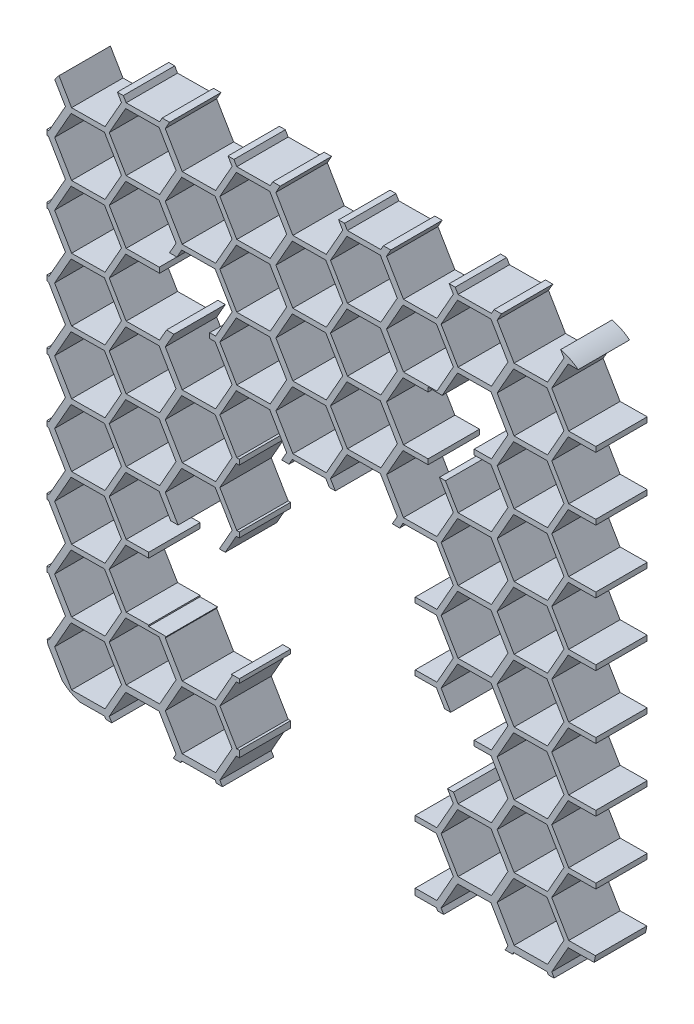
SolidWorks part; units mm, degrees
ref_plane "Front Plane" through (0, 0, 0) normal (0, 0, 1) x (1, 0, 0)
ref_plane "Top Plane" through (0, 0, 0) normal (0, 1, 0) x (1, 0, 0)
ref_plane "Right Plane" through (0, 0, 0) normal (1, 0, 0) x (0, 0, -1)
sketch "Sketch4" plane through (0, 0, 0) normal (0, 0, 1) x (1, 0, 0)
  line L8 (-54.4, 44.4) -> (-54.4, -44.4)
  line L9 (-44.4, -54.4) -> (44.4, -54.4)
  line L10 (54.4, -44.4) -> (54.4, 44.4)
  line L11 (44.4, 54.4) -> (-44.4, 54.4)
  line L12 (-53.4, -44.4) -> (-53.4, 44.4)
  line L13 (-44.4, -53.4) -> (44.4, -53.4)
  line L14 (53.4, -44.4) -> (53.4, 44.4)
  line L15 (-44.4, 53.4) -> (44.4, 53.4)
  arc A8 (-44.4, 54.4) -> (-54.4, 44.4) centre (-44.4, 44.4) ccw
  arc A9 (-54.4, -44.4) -> (-44.4, -54.4) centre (-44.4, -44.4) ccw
  arc A10 (44.4, -54.4) -> (54.4, -44.4) centre (44.4, -44.4) ccw
  arc A11 (54.4, 44.4) -> (44.4, 54.4) centre (44.4, 44.4) ccw
  arc A12 (-53.4, -44.4) -> (-44.4, -53.4) centre (-44.4, -44.4) ccw
  arc A13 (44.4, -53.4) -> (53.4, -44.4) centre (44.4, -44.4) ccw
  arc A14 (53.4, 44.4) -> (44.4, 53.4) centre (44.4, 44.4) ccw
  arc A15 (-44.4, 53.4) -> (-53.4, 44.4) centre (-44.4, 44.4) ccw
sketch "Sketch5" plane through (0, 0, 0) normal (0, 0, 1) x (1, 0, 0)
  line L0 (-28.256, 33.6476) -> (-31.5557, 39.2481)
  line L1 (-38.8735, 27.5176) -> (-42.1732, 33.1181)
  line L2 (-42.1732, 33.1181) -> (-48.6732, 33.0607)
  line L3 (-48.6732, 33.0607) -> (-51.8735, 27.4029)
  line L4 (-51.8735, 27.4029) -> (-48.5738, 21.8024)
  line L5 (-48.5738, 21.8024) -> (-42.0738, 21.8597)
  line L6 (-42.0738, 21.8597) -> (-38.8735, 27.5176)
  line L7 (-31.5557, 39.2481) -> (-38.0557, 39.1907)
  line L8 (-38.0557, 39.1907) -> (-41.256, 33.5329)
  line L9 (-41.256, 33.5329) -> (-37.9563, 27.9324)
  line L10 (-37.9563, 27.9324) -> (-31.4563, 27.9897)
  line L11 (-31.4563, 27.9897) -> (-28.256, 33.6476)
  line L12 (-38.8735, 27.5176) -> (-28.256, 33.6476) construction
  line L13 (-28.256, 45.9076) -> (-31.5557, 51.5081)
  line L14 (-38.8735, 39.7776) -> (-42.1732, 45.3781)
  line L15 (-42.1732, 45.3781) -> (-48.6732, 45.3207)
  line L16 (-48.6732, 45.3207) -> (-51.8735, 39.6629)
  line L17 (-51.8735, 39.6629) -> (-48.5738, 34.0624)
  line L18 (-48.5738, 34.0624) -> (-42.0738, 34.1197)
  line L19 (-42.0738, 34.1197) -> (-38.8735, 39.7776)
  line L20 (-31.5557, 51.5081) -> (-38.0557, 51.4507)
  line L21 (-38.0557, 51.4507) -> (-41.256, 45.7929)
  line L22 (-41.256, 45.7929) -> (-37.9563, 40.1924)
  line L23 (-37.9563, 40.1924) -> (-31.4563, 40.2497)
  line L24 (-31.4563, 40.2497) -> (-28.256, 45.9076)
  line L25 (-38.8735, 39.7776) -> (-28.256, 45.9076) construction
  line L26 (-6.736, 33.6476) -> (-10.0357, 39.2481)
  line L27 (-17.3535, 27.5176) -> (-20.6532, 33.1181)
  line L28 (-20.6532, 33.1181) -> (-27.1532, 33.0607)
  line L29 (-27.1532, 33.0607) -> (-30.3535, 27.4029)
  line L30 (-30.3535, 27.4029) -> (-27.0538, 21.8024)
  line L31 (-27.0538, 21.8024) -> (-20.5538, 21.8597)
  line L32 (-20.5538, 21.8597) -> (-17.3535, 27.5176)
  line L33 (-10.0357, 39.2481) -> (-16.5357, 39.1907)
  line L34 (-16.5357, 39.1907) -> (-19.736, 33.5329)
  line L35 (-19.736, 33.5329) -> (-16.4363, 27.9324)
  line L36 (-16.4363, 27.9324) -> (-9.9363, 27.9897)
  line L37 (-9.9363, 27.9897) -> (-6.736, 33.6476)
  line L38 (-6.736, 45.9076) -> (-10.0357, 51.5081)
  line L39 (-17.3535, 39.7776) -> (-20.6532, 45.3781)
  line L40 (-20.6532, 45.3781) -> (-27.1532, 45.3207)
  line L41 (-27.1532, 45.3207) -> (-30.3535, 39.6629)
  line L42 (-30.3535, 39.6629) -> (-27.0538, 34.0624)
  line L43 (-27.0538, 34.0624) -> (-20.5538, 34.1197)
  line L44 (-20.5538, 34.1197) -> (-17.3535, 39.7776)
  line L45 (-10.0357, 51.5081) -> (-16.5357, 51.4507)
  line L46 (-16.5357, 51.4507) -> (-19.736, 45.7929)
  line L47 (-19.736, 45.7929) -> (-16.4363, 40.1924)
  line L48 (-16.4363, 40.1924) -> (-9.9363, 40.2497)
  line L49 (-9.9363, 40.2497) -> (-6.736, 45.9076)
  line L50 (-17.3535, 27.5176) -> (-6.736, 33.6476) construction
  line L51 (-17.3535, 39.7776) -> (-6.736, 45.9076) construction
  line L52 (14.784, 33.6476) -> (11.4843, 39.2481)
  line L53 (4.1665, 27.5176) -> (0.8668, 33.1181)
  line L54 (0.8668, 33.1181) -> (-5.6332, 33.0607)
  line L55 (-5.6332, 33.0607) -> (-8.8335, 27.4029)
  line L56 (-8.8335, 27.4029) -> (-5.5338, 21.8024)
  line L57 (-5.5338, 21.8024) -> (0.9662, 21.8597)
  line L58 (0.9662, 21.8597) -> (4.1665, 27.5176)
  line L59 (11.4843, 39.2481) -> (4.9843, 39.1907)
  line L60 (4.9843, 39.1907) -> (1.784, 33.5329)
  line L61 (1.784, 33.5329) -> (5.0837, 27.9324)
  line L62 (5.0837, 27.9324) -> (11.5837, 27.9897)
  line L63 (11.5837, 27.9897) -> (14.784, 33.6476)
  line L64 (14.784, 45.9076) -> (11.4843, 51.5081)
  line L65 (4.1665, 39.7776) -> (0.8668, 45.3781)
  line L66 (0.8668, 45.3781) -> (-5.6332, 45.3207)
  line L67 (-5.6332, 45.3207) -> (-8.8335, 39.6629)
  line L68 (-8.8335, 39.6629) -> (-5.5338, 34.0624)
  line L69 (-5.5338, 34.0624) -> (0.9662, 34.1197)
  line L70 (0.9662, 34.1197) -> (4.1665, 39.7776)
  line L71 (11.4843, 51.5081) -> (4.9843, 51.4507)
  line L72 (4.9843, 51.4507) -> (1.784, 45.7929)
  line L73 (1.784, 45.7929) -> (5.0837, 40.1924)
  line L74 (5.0837, 40.1924) -> (11.5837, 40.2497)
  line L75 (11.5837, 40.2497) -> (14.784, 45.9076)
  line L76 (4.1665, 27.5176) -> (14.784, 33.6476) construction
  line L77 (4.1665, 39.7776) -> (14.784, 45.9076) construction
  line L78 (36.304, 33.6476) -> (33.0043, 39.2481)
  line L79 (25.6865, 27.5176) -> (22.3868, 33.1181)
  line L80 (22.3868, 33.1181) -> (15.8868, 33.0607)
  line L81 (15.8868, 33.0607) -> (12.6865, 27.4029)
  line L82 (12.6865, 27.4029) -> (15.9862, 21.8024)
  line L83 (15.9862, 21.8024) -> (22.4862, 21.8597)
  line L84 (22.4862, 21.8597) -> (25.6865, 27.5176)
  line L85 (33.0043, 39.2481) -> (26.5043, 39.1907)
  line L86 (26.5043, 39.1907) -> (23.304, 33.5329)
  line L87 (23.304, 33.5329) -> (26.6037, 27.9324)
  line L88 (26.6037, 27.9324) -> (33.1037, 27.9897)
  line L89 (33.1037, 27.9897) -> (36.304, 33.6476)
  line L90 (36.304, 45.9076) -> (33.0043, 51.5081)
  line L91 (25.6865, 39.7776) -> (22.3868, 45.3781)
  line L92 (22.3868, 45.3781) -> (15.8868, 45.3207)
  line L93 (15.8868, 45.3207) -> (12.6865, 39.6629)
  line L94 (12.6865, 39.6629) -> (15.9862, 34.0624)
  line L95 (15.9862, 34.0624) -> (22.4862, 34.1197)
  line L96 (22.4862, 34.1197) -> (25.6865, 39.7776)
  line L97 (33.0043, 51.5081) -> (26.5043, 51.4507)
  line L98 (26.5043, 51.4507) -> (23.304, 45.7929)
  line L99 (23.304, 45.7929) -> (26.6037, 40.1924)
  line L100 (26.6037, 40.1924) -> (33.1037, 40.2497)
  line L101 (33.1037, 40.2497) -> (36.304, 45.9076)
  line L102 (25.6865, 27.5176) -> (36.304, 33.6476) construction
  line L103 (25.6865, 39.7776) -> (36.304, 45.9076) construction
  line L104 (57.824, 33.6476) -> (54.5243, 39.2481)
  line L105 (47.2065, 27.5176) -> (43.9068, 33.1181)
  line L106 (43.9068, 33.1181) -> (37.4068, 33.0607)
  line L107 (37.4068, 33.0607) -> (34.2065, 27.4029)
  line L108 (34.2065, 27.4029) -> (37.5062, 21.8024)
  line L109 (37.5062, 21.8024) -> (44.0062, 21.8597)
  line L110 (44.0062, 21.8597) -> (47.2065, 27.5176)
  line L111 (54.5243, 39.2481) -> (48.0243, 39.1907)
  line L112 (48.0243, 39.1907) -> (44.824, 33.5329)
  line L113 (44.824, 33.5329) -> (48.1237, 27.9324)
  line L114 (48.1237, 27.9324) -> (54.6237, 27.9897)
  line L115 (54.6237, 27.9897) -> (57.824, 33.6476)
  line L116 (57.824, 45.9076) -> (54.5243, 51.5081)
  line L117 (47.2065, 39.7776) -> (43.9068, 45.3781)
  line L118 (43.9068, 45.3781) -> (37.4068, 45.3207)
  line L119 (37.4068, 45.3207) -> (34.2065, 39.6629)
  line L120 (34.2065, 39.6629) -> (37.5062, 34.0624)
  line L121 (37.5062, 34.0624) -> (44.0062, 34.1197)
  line L122 (44.0062, 34.1197) -> (47.2065, 39.7776)
  line L123 (54.5243, 51.5081) -> (48.0243, 51.4507)
  line L124 (48.0243, 51.4507) -> (44.824, 45.7929)
  line L125 (44.824, 45.7929) -> (48.1237, 40.1924)
  line L126 (48.1237, 40.1924) -> (54.6237, 40.2497)
  line L127 (54.6237, 40.2497) -> (57.824, 45.9076)
  line L128 (47.2065, 27.5176) -> (57.824, 33.6476) construction
  line L129 (47.2065, 39.7776) -> (57.824, 45.9076) construction
  line L130 (-6.736, 9.1276) -> (-10.0357, 14.7281)
  line L131 (-17.3535, 2.9976) -> (-20.6532, 8.5981)
  line L132 (-20.6532, 8.5981) -> (-27.1532, 8.5407)
  line L133 (-27.1532, 8.5407) -> (-30.3535, 2.8829)
  line L134 (-30.3535, 2.8829) -> (-27.0538, -2.7176)
  line L135 (-27.0538, -2.7176) -> (-20.5538, -2.6603)
  line L136 (-20.5538, -2.6603) -> (-17.3535, 2.9976)
  line L137 (-10.0357, 14.7281) -> (-16.5357, 14.6707)
  line L138 (-16.5357, 14.6707) -> (-19.736, 9.0129)
  line L139 (-19.736, 9.0129) -> (-16.4363, 3.4124)
  line L140 (-16.4363, 3.4124) -> (-9.9363, 3.4697)
  line L141 (-9.9363, 3.4697) -> (-6.736, 9.1276)
  line L142 (-6.736, 21.3876) -> (-10.0357, 26.9881)
  line L143 (-17.3535, 15.2576) -> (-20.6532, 20.8581)
  line L144 (-20.6532, 20.8581) -> (-27.1532, 20.8007)
  line L145 (-27.1532, 20.8007) -> (-30.3535, 15.1429)
  line L146 (-30.3535, 15.1429) -> (-27.0538, 9.5424)
  line L147 (-27.0538, 9.5424) -> (-20.5538, 9.5997)
  line L148 (-20.5538, 9.5997) -> (-17.3535, 15.2576)
  line L149 (-10.0357, 26.9881) -> (-16.5357, 26.9307)
  line L150 (-16.5357, 26.9307) -> (-19.736, 21.2729)
  line L151 (-19.736, 21.2729) -> (-16.4363, 15.6724)
  line L152 (-16.4363, 15.6724) -> (-9.9363, 15.7297)
  line L153 (-9.9363, 15.7297) -> (-6.736, 21.3876)
  line L154 (-17.3535, 2.9976) -> (-6.736, 9.1276) construction
  line L155 (-17.3535, 15.2576) -> (-6.736, 21.3876) construction
  line L156 (14.784, 9.1276) -> (11.4843, 14.7281)
  line L157 (4.1665, 2.9976) -> (0.8668, 8.5981)
  line L158 (0.8668, 8.5981) -> (-5.6332, 8.5407)
  line L159 (-5.6332, 8.5407) -> (-8.8335, 2.8829)
  line L160 (-8.8335, 2.8829) -> (-5.5338, -2.7176)
  line L161 (-5.5338, -2.7176) -> (0.9662, -2.6603)
  line L162 (0.9662, -2.6603) -> (4.1665, 2.9976)
  line L163 (11.4843, 14.7281) -> (4.9843, 14.6707)
  line L164 (4.9843, 14.6707) -> (1.784, 9.0129)
  line L165 (1.784, 9.0129) -> (5.0837, 3.4124)
  line L166 (5.0837, 3.4124) -> (11.5837, 3.4697)
  line L167 (11.5837, 3.4697) -> (14.784, 9.1276)
  line L168 (14.784, 21.3876) -> (11.4843, 26.9881)
  line L169 (4.1665, 15.2576) -> (0.8668, 20.8581)
  line L170 (0.8668, 20.8581) -> (-5.6332, 20.8007)
  line L171 (-5.6332, 20.8007) -> (-8.8335, 15.1429)
  line L172 (-8.8335, 15.1429) -> (-5.5338, 9.5424)
  line L173 (-5.5338, 9.5424) -> (0.9662, 9.5997)
  line L174 (0.9662, 9.5997) -> (4.1665, 15.2576)
  line L175 (11.4843, 26.9881) -> (4.9843, 26.9307)
  line L176 (4.9843, 26.9307) -> (1.784, 21.2729)
  line L177 (1.784, 21.2729) -> (5.0837, 15.6724)
  line L178 (5.0837, 15.6724) -> (11.5837, 15.7297)
  line L179 (11.5837, 15.7297) -> (14.784, 21.3876)
  line L180 (4.1665, 2.9976) -> (14.784, 9.1276) construction
  line L181 (4.1665, 15.2576) -> (14.784, 21.3876) construction
  line L182 (36.304, 9.1276) -> (33.0043, 14.7281)
  line L183 (25.6865, 2.9976) -> (22.3868, 8.5981)
  line L184 (22.3868, 8.5981) -> (15.8868, 8.5407)
  line L185 (15.8868, 8.5407) -> (12.6865, 2.8829)
  line L186 (12.6865, 2.8829) -> (15.9862, -2.7176)
  line L187 (15.9862, -2.7176) -> (22.4862, -2.6603)
  line L188 (22.4862, -2.6603) -> (25.6865, 2.9976)
  line L189 (33.0043, 14.7281) -> (26.5043, 14.6707)
  line L190 (26.5043, 14.6707) -> (23.304, 9.0129)
  line L191 (23.304, 9.0129) -> (26.6037, 3.4124)
  line L192 (26.6037, 3.4124) -> (33.1037, 3.4697)
  line L193 (33.1037, 3.4697) -> (36.304, 9.1276)
  line L194 (36.304, 21.3876) -> (33.0043, 26.9881)
  line L195 (25.6865, 15.2576) -> (22.3868, 20.8581)
  line L196 (22.3868, 20.8581) -> (15.8868, 20.8007)
  line L197 (15.8868, 20.8007) -> (12.6865, 15.1429)
  line L198 (12.6865, 15.1429) -> (15.9862, 9.5424)
  line L199 (15.9862, 9.5424) -> (22.4862, 9.5997)
  line L200 (22.4862, 9.5997) -> (25.6865, 15.2576)
  line L201 (33.0043, 26.9881) -> (26.5043, 26.9307)
  line L202 (26.5043, 26.9307) -> (23.304, 21.2729)
  line L203 (23.304, 21.2729) -> (26.6037, 15.6724)
  line L204 (26.6037, 15.6724) -> (33.1037, 15.7297)
  line L205 (33.1037, 15.7297) -> (36.304, 21.3876)
  line L206 (25.6865, 2.9976) -> (36.304, 9.1276) construction
  line L207 (25.6865, 15.2576) -> (36.304, 21.3876) construction
  line L208 (57.824, 9.1276) -> (54.5243, 14.7281)
  line L209 (47.2065, 2.9976) -> (43.9068, 8.5981)
  line L210 (43.9068, 8.5981) -> (37.4068, 8.5407)
  line L211 (37.4068, 8.5407) -> (34.2065, 2.8829)
  line L212 (34.2065, 2.8829) -> (37.5062, -2.7176)
  line L213 (37.5062, -2.7176) -> (44.0062, -2.6603)
  line L214 (44.0062, -2.6603) -> (47.2065, 2.9976)
  line L215 (54.5243, 14.7281) -> (48.0243, 14.6707)
  line L216 (48.0243, 14.6707) -> (44.824, 9.0129)
  line L217 (44.824, 9.0129) -> (48.1237, 3.4124)
  line L218 (48.1237, 3.4124) -> (54.6237, 3.4697)
  line L219 (54.6237, 3.4697) -> (57.824, 9.1276)
  line L220 (57.824, 21.3876) -> (54.5243, 26.9881)
  line L221 (47.2065, 15.2576) -> (43.9068, 20.8581)
  line L222 (43.9068, 20.8581) -> (37.4068, 20.8007)
  line L223 (37.4068, 20.8007) -> (34.2065, 15.1429)
  line L224 (34.2065, 15.1429) -> (37.5062, 9.5424)
  line L225 (37.5062, 9.5424) -> (44.0062, 9.5997)
  line L226 (44.0062, 9.5997) -> (47.2065, 15.2576)
  line L227 (54.5243, 26.9881) -> (48.0243, 26.9307)
  line L228 (48.0243, 26.9307) -> (44.824, 21.2729)
  line L229 (44.824, 21.2729) -> (48.1237, 15.6724)
  line L230 (48.1237, 15.6724) -> (54.6237, 15.7297)
  line L231 (54.6237, 15.7297) -> (57.824, 21.3876)
  line L232 (47.2065, 2.9976) -> (57.824, 9.1276) construction
  line L233 (47.2065, 15.2576) -> (57.824, 21.3876) construction
  line L234 (-6.736, -15.3924) -> (-10.0357, -9.7919)
  line L235 (-17.3535, -21.5224) -> (-20.6532, -15.9219)
  line L236 (-20.6532, -15.9219) -> (-27.1532, -15.9793)
  line L237 (-27.1532, -15.9793) -> (-30.3535, -21.6371)
  line L238 (-30.3535, -21.6371) -> (-27.0538, -27.2376)
  line L239 (-27.0538, -27.2376) -> (-20.5538, -27.1803)
  line L240 (-20.5538, -27.1803) -> (-17.3535, -21.5224)
  line L241 (-10.0357, -9.7919) -> (-16.5357, -9.8493)
  line L242 (-16.5357, -9.8493) -> (-19.736, -15.5071)
  line L243 (-19.736, -15.5071) -> (-16.4363, -21.1076)
  line L244 (-16.4363, -21.1076) -> (-9.9363, -21.0503)
  line L245 (-9.9363, -21.0503) -> (-6.736, -15.3924)
  line L246 (-6.736, -3.1324) -> (-10.0357, 2.4681)
  line L247 (-17.3535, -9.2624) -> (-20.6532, -3.6619)
  line L248 (-20.6532, -3.6619) -> (-27.1532, -3.7193)
  line L249 (-27.1532, -3.7193) -> (-30.3535, -9.3771)
  line L250 (-30.3535, -9.3771) -> (-27.0538, -14.9776)
  line L251 (-27.0538, -14.9776) -> (-20.5538, -14.9203)
  line L252 (-20.5538, -14.9203) -> (-17.3535, -9.2624)
  line L253 (-10.0357, 2.4681) -> (-16.5357, 2.4107)
  line L254 (-16.5357, 2.4107) -> (-19.736, -3.2471)
  line L255 (-19.736, -3.2471) -> (-16.4363, -8.8476)
  line L256 (-16.4363, -8.8476) -> (-9.9363, -8.7903)
  line L257 (-9.9363, -8.7903) -> (-6.736, -3.1324)
  line L258 (-17.3535, -21.5224) -> (-6.736, -15.3924) construction
  line L259 (-17.3535, -9.2624) -> (-6.736, -3.1324) construction
  line L260 (14.784, -15.3924) -> (11.4843, -9.7919)
  line L261 (4.1665, -21.5224) -> (0.8668, -15.9219)
  line L262 (0.8668, -15.9219) -> (-5.6332, -15.9793)
  line L263 (-5.6332, -15.9793) -> (-8.8335, -21.6371)
  line L264 (-8.8335, -21.6371) -> (-5.5338, -27.2376)
  line L265 (-5.5338, -27.2376) -> (0.9662, -27.1803)
  line L266 (0.9662, -27.1803) -> (4.1665, -21.5224)
  line L267 (11.4843, -9.7919) -> (4.9843, -9.8493)
  line L268 (4.9843, -9.8493) -> (1.784, -15.5071)
  line L269 (1.784, -15.5071) -> (5.0837, -21.1076)
  line L270 (5.0837, -21.1076) -> (11.5837, -21.0503)
  line L271 (11.5837, -21.0503) -> (14.784, -15.3924)
  line L272 (14.784, -3.1324) -> (11.4843, 2.4681)
  line L273 (4.1665, -9.2624) -> (0.8668, -3.6619)
  line L274 (0.8668, -3.6619) -> (-5.6332, -3.7193)
  line L275 (-5.6332, -3.7193) -> (-8.8335, -9.3771)
  line L276 (-8.8335, -9.3771) -> (-5.5338, -14.9776)
  line L277 (-5.5338, -14.9776) -> (0.9662, -14.9203)
  line L278 (0.9662, -14.9203) -> (4.1665, -9.2624)
  line L279 (11.4843, 2.4681) -> (4.9843, 2.4107)
  line L280 (4.9843, 2.4107) -> (1.784, -3.2471)
  line L281 (1.784, -3.2471) -> (5.0837, -8.8476)
  line L282 (5.0837, -8.8476) -> (11.5837, -8.7903)
  line L283 (11.5837, -8.7903) -> (14.784, -3.1324)
  line L284 (4.1665, -21.5224) -> (14.784, -15.3924) construction
  line L285 (4.1665, -9.2624) -> (14.784, -3.1324) construction
  line L286 (36.304, -15.3924) -> (33.0043, -9.7919)
  line L287 (25.6865, -21.5224) -> (22.3868, -15.9219)
  line L288 (22.3868, -15.9219) -> (15.8868, -15.9793)
  line L289 (15.8868, -15.9793) -> (12.6865, -21.6371)
  line L290 (12.6865, -21.6371) -> (15.9862, -27.2376)
  line L291 (15.9862, -27.2376) -> (22.4862, -27.1803)
  line L292 (22.4862, -27.1803) -> (25.6865, -21.5224)
  line L293 (33.0043, -9.7919) -> (26.5043, -9.8493)
  line L294 (26.5043, -9.8493) -> (23.304, -15.5071)
  line L295 (23.304, -15.5071) -> (26.6037, -21.1076)
  line L296 (26.6037, -21.1076) -> (33.1037, -21.0503)
  line L297 (33.1037, -21.0503) -> (36.304, -15.3924)
  line L298 (36.304, -3.1324) -> (33.0043, 2.4681)
  line L299 (25.6865, -9.2624) -> (22.3868, -3.6619)
  line L300 (22.3868, -3.6619) -> (15.8868, -3.7193)
  line L301 (15.8868, -3.7193) -> (12.6865, -9.3771)
  line L302 (12.6865, -9.3771) -> (15.9862, -14.9776)
  line L303 (15.9862, -14.9776) -> (22.4862, -14.9203)
  line L304 (22.4862, -14.9203) -> (25.6865, -9.2624)
  line L305 (33.0043, 2.4681) -> (26.5043, 2.4107)
  line L306 (26.5043, 2.4107) -> (23.304, -3.2471)
  line L307 (23.304, -3.2471) -> (26.6037, -8.8476)
  line L308 (26.6037, -8.8476) -> (33.1037, -8.7903)
  line L309 (33.1037, -8.7903) -> (36.304, -3.1324)
  line L310 (25.6865, -21.5224) -> (36.304, -15.3924) construction
  line L311 (25.6865, -9.2624) -> (36.304, -3.1324) construction
  line L312 (57.824, -15.3924) -> (54.5243, -9.7919)
  line L313 (47.2065, -21.5224) -> (43.9068, -15.9219)
  line L314 (43.9068, -15.9219) -> (37.4068, -15.9793)
  line L315 (37.4068, -15.9793) -> (34.2065, -21.6371)
  line L316 (34.2065, -21.6371) -> (37.5062, -27.2376)
  line L317 (37.5062, -27.2376) -> (44.0062, -27.1803)
  line L318 (44.0062, -27.1803) -> (47.2065, -21.5224)
  line L319 (54.5243, -9.7919) -> (48.0243, -9.8493)
  line L320 (48.0243, -9.8493) -> (44.824, -15.5071)
  line L321 (44.824, -15.5071) -> (48.1237, -21.1076)
  line L322 (48.1237, -21.1076) -> (54.6237, -21.0503)
  line L323 (54.6237, -21.0503) -> (57.824, -15.3924)
  line L324 (57.824, -3.1324) -> (54.5243, 2.4681)
  line L325 (47.2065, -9.2624) -> (43.9068, -3.6619)
  line L326 (43.9068, -3.6619) -> (37.4068, -3.7193)
  line L327 (37.4068, -3.7193) -> (34.2065, -9.3771)
  line L328 (34.2065, -9.3771) -> (37.5062, -14.9776)
  line L329 (37.5062, -14.9776) -> (44.0062, -14.9203)
  line L330 (44.0062, -14.9203) -> (47.2065, -9.2624)
  line L331 (54.5243, 2.4681) -> (48.0243, 2.4107)
  line L332 (48.0243, 2.4107) -> (44.824, -3.2471)
  line L333 (44.824, -3.2471) -> (48.1237, -8.8476)
  line L334 (48.1237, -8.8476) -> (54.6237, -8.7903)
  line L335 (54.6237, -8.7903) -> (57.824, -3.1324)
  line L336 (47.2065, -21.5224) -> (57.824, -15.3924) construction
  line L337 (47.2065, -9.2624) -> (57.824, -3.1324) construction
  line L338 (-6.736, -39.9124) -> (-10.0357, -34.3119)
  line L339 (-17.3535, -46.0424) -> (-20.6532, -40.4419)
  line L340 (-20.6532, -40.4419) -> (-27.1532, -40.4993)
  line L341 (-27.1532, -40.4993) -> (-30.3535, -46.1571)
  line L342 (-30.3535, -46.1571) -> (-27.0538, -51.7576)
  line L343 (-27.0538, -51.7576) -> (-20.5538, -51.7003)
  line L344 (-20.5538, -51.7003) -> (-17.3535, -46.0424)
  line L345 (-10.0357, -34.3119) -> (-16.5357, -34.3693)
  line L346 (-16.5357, -34.3693) -> (-19.736, -40.0271)
  line L347 (-19.736, -40.0271) -> (-16.4363, -45.6276)
  line L348 (-16.4363, -45.6276) -> (-9.9363, -45.5703)
  line L349 (-9.9363, -45.5703) -> (-6.736, -39.9124)
  line L350 (-6.736, -27.6524) -> (-10.0357, -22.0519)
  line L351 (-17.3535, -33.7824) -> (-20.6532, -28.1819)
  line L352 (-20.6532, -28.1819) -> (-27.1532, -28.2393)
  line L353 (-27.1532, -28.2393) -> (-30.3535, -33.8971)
  line L354 (-30.3535, -33.8971) -> (-27.0538, -39.4976)
  line L355 (-27.0538, -39.4976) -> (-20.5538, -39.4403)
  line L356 (-20.5538, -39.4403) -> (-17.3535, -33.7824)
  line L357 (-10.0357, -22.0519) -> (-16.5357, -22.1093)
  line L358 (-16.5357, -22.1093) -> (-19.736, -27.7671)
  line L359 (-19.736, -27.7671) -> (-16.4363, -33.3676)
  line L360 (-16.4363, -33.3676) -> (-9.9363, -33.3103)
  line L361 (-9.9363, -33.3103) -> (-6.736, -27.6524)
  line L362 (-17.3535, -46.0424) -> (-6.736, -39.9124) construction
  line L363 (-17.3535, -33.7824) -> (-6.736, -27.6524) construction
  line L364 (14.784, -39.9124) -> (11.4843, -34.3119)
  line L365 (4.1665, -46.0424) -> (0.8668, -40.4419)
  line L366 (0.8668, -40.4419) -> (-5.6332, -40.4993)
  line L367 (-5.6332, -40.4993) -> (-8.8335, -46.1571)
  line L368 (-8.8335, -46.1571) -> (-5.5338, -51.7576)
  line L369 (-5.5338, -51.7576) -> (0.9662, -51.7003)
  line L370 (0.9662, -51.7003) -> (4.1665, -46.0424)
  line L371 (11.4843, -34.3119) -> (4.9843, -34.3693)
  line L372 (4.9843, -34.3693) -> (1.784, -40.0271)
  line L373 (1.784, -40.0271) -> (5.0837, -45.6276)
  line L374 (5.0837, -45.6276) -> (11.5837, -45.5703)
  line L375 (11.5837, -45.5703) -> (14.784, -39.9124)
  line L376 (14.784, -27.6524) -> (11.4843, -22.0519)
  line L377 (4.1665, -33.7824) -> (0.8668, -28.1819)
  line L378 (0.8668, -28.1819) -> (-5.6332, -28.2393)
  line L379 (-5.6332, -28.2393) -> (-8.8335, -33.8971)
  line L380 (-8.8335, -33.8971) -> (-5.5338, -39.4976)
  line L381 (-5.5338, -39.4976) -> (0.9662, -39.4403)
  line L382 (0.9662, -39.4403) -> (4.1665, -33.7824)
  line L383 (11.4843, -22.0519) -> (4.9843, -22.1093)
  line L384 (4.9843, -22.1093) -> (1.784, -27.7671)
  line L385 (1.784, -27.7671) -> (5.0837, -33.3676)
  line L386 (5.0837, -33.3676) -> (11.5837, -33.3103)
  line L387 (11.5837, -33.3103) -> (14.784, -27.6524)
  line L388 (4.1665, -46.0424) -> (14.784, -39.9124) construction
  line L389 (4.1665, -33.7824) -> (14.784, -27.6524) construction
  line L390 (36.304, -39.9124) -> (33.0043, -34.3119)
  line L391 (25.6865, -46.0424) -> (22.3868, -40.4419)
  line L392 (22.3868, -40.4419) -> (15.8868, -40.4993)
  line L393 (15.8868, -40.4993) -> (12.6865, -46.1571)
  line L394 (12.6865, -46.1571) -> (15.9862, -51.7576)
  line L395 (15.9862, -51.7576) -> (22.4862, -51.7003)
  line L396 (22.4862, -51.7003) -> (25.6865, -46.0424)
  line L397 (33.0043, -34.3119) -> (26.5043, -34.3693)
  line L398 (26.5043, -34.3693) -> (23.304, -40.0271)
  line L399 (23.304, -40.0271) -> (26.6037, -45.6276)
  line L400 (26.6037, -45.6276) -> (33.1037, -45.5703)
  line L401 (33.1037, -45.5703) -> (36.304, -39.9124)
  line L402 (36.304, -27.6524) -> (33.0043, -22.0519)
  line L403 (25.6865, -33.7824) -> (22.3868, -28.1819)
  line L404 (22.3868, -28.1819) -> (15.8868, -28.2393)
  line L405 (15.8868, -28.2393) -> (12.6865, -33.8971)
  line L406 (12.6865, -33.8971) -> (15.9862, -39.4976)
  line L407 (15.9862, -39.4976) -> (22.4862, -39.4403)
  line L408 (22.4862, -39.4403) -> (25.6865, -33.7824)
  line L409 (33.0043, -22.0519) -> (26.5043, -22.1093)
  line L410 (26.5043, -22.1093) -> (23.304, -27.7671)
  line L411 (23.304, -27.7671) -> (26.6037, -33.3676)
  line L412 (26.6037, -33.3676) -> (33.1037, -33.3103)
  line L413 (33.1037, -33.3103) -> (36.304, -27.6524)
  line L414 (25.6865, -46.0424) -> (36.304, -39.9124) construction
  line L415 (25.6865, -33.7824) -> (36.304, -27.6524) construction
  line L416 (57.824, -39.9124) -> (54.5243, -34.3119)
  line L417 (47.2065, -46.0424) -> (43.9068, -40.4419)
  line L418 (43.9068, -40.4419) -> (37.4068, -40.4993)
  line L419 (37.4068, -40.4993) -> (34.2065, -46.1571)
  line L420 (34.2065, -46.1571) -> (37.5062, -51.7576)
  line L421 (37.5062, -51.7576) -> (44.0062, -51.7003)
  line L422 (44.0062, -51.7003) -> (47.2065, -46.0424)
  line L423 (54.5243, -34.3119) -> (48.0243, -34.3693)
  line L424 (48.0243, -34.3693) -> (44.824, -40.0271)
  line L425 (44.824, -40.0271) -> (48.1237, -45.6276)
  line L426 (48.1237, -45.6276) -> (54.6237, -45.5703)
  line L427 (54.6237, -45.5703) -> (57.824, -39.9124)
  line L428 (57.824, -27.6524) -> (54.5243, -22.0519)
  line L429 (47.2065, -33.7824) -> (43.9068, -28.1819)
  line L430 (43.9068, -28.1819) -> (37.4068, -28.2393)
  line L431 (37.4068, -28.2393) -> (34.2065, -33.8971)
  line L432 (34.2065, -33.8971) -> (37.5062, -39.4976)
  line L433 (37.5062, -39.4976) -> (44.0062, -39.4403)
  line L434 (44.0062, -39.4403) -> (47.2065, -33.7824)
  line L435 (54.5243, -22.0519) -> (48.0243, -22.1093)
  line L436 (48.0243, -22.1093) -> (44.824, -27.7671)
  line L437 (44.824, -27.7671) -> (48.1237, -33.3676)
  line L438 (48.1237, -33.3676) -> (54.6237, -33.3103)
  line L439 (54.6237, -33.3103) -> (57.824, -27.6524)
  line L440 (47.2065, -46.0424) -> (57.824, -39.9124) construction
  line L441 (47.2065, -33.7824) -> (57.824, -27.6524) construction
  line L442 (-28.256, 9.1276) -> (-31.5557, 14.7281)
  line L443 (-38.8735, 2.9976) -> (-42.1732, 8.5981)
  line L444 (-42.1732, 8.5981) -> (-48.6732, 8.5407)
  line L445 (-48.6732, 8.5407) -> (-51.8735, 2.8829)
  line L446 (-51.8735, 2.8829) -> (-48.5738, -2.7176)
  line L447 (-48.5738, -2.7176) -> (-42.0738, -2.6603)
  line L448 (-42.0738, -2.6603) -> (-38.8735, 2.9976)
  line L449 (-31.5557, 14.7281) -> (-38.0557, 14.6707)
  line L450 (-38.0557, 14.6707) -> (-41.256, 9.0129)
  line L451 (-41.256, 9.0129) -> (-37.9563, 3.4124)
  line L452 (-37.9563, 3.4124) -> (-31.4563, 3.4697)
  line L453 (-31.4563, 3.4697) -> (-28.256, 9.1276)
  line L454 (-28.256, 21.3876) -> (-31.5557, 26.9881)
  line L455 (-38.8735, 15.2576) -> (-42.1732, 20.8581)
  line L456 (-42.1732, 20.8581) -> (-48.6732, 20.8007)
  line L457 (-48.6732, 20.8007) -> (-51.8735, 15.1429)
  line L458 (-51.8735, 15.1429) -> (-48.5738, 9.5424)
  line L459 (-48.5738, 9.5424) -> (-42.0738, 9.5997)
  line L460 (-42.0738, 9.5997) -> (-38.8735, 15.2576)
  line L461 (-31.5557, 26.9881) -> (-38.0557, 26.9307)
  line L462 (-38.0557, 26.9307) -> (-41.256, 21.2729)
  line L463 (-41.256, 21.2729) -> (-37.9563, 15.6724)
  line L464 (-37.9563, 15.6724) -> (-31.4563, 15.7297)
  line L465 (-31.4563, 15.7297) -> (-28.256, 21.3876)
  line L466 (-38.8735, 2.9976) -> (-28.256, 9.1276) construction
  line L467 (-38.8735, 15.2576) -> (-28.256, 21.3876) construction
  line L468 (-28.256, -15.3924) -> (-31.5557, -9.7919)
  line L469 (-38.8735, -21.5224) -> (-42.1732, -15.9219)
  line L470 (-42.1732, -15.9219) -> (-48.6732, -15.9793)
  line L471 (-48.6732, -15.9793) -> (-51.8735, -21.6371)
  line L472 (-51.8735, -21.6371) -> (-48.5738, -27.2376)
  line L473 (-48.5738, -27.2376) -> (-42.0738, -27.1803)
  line L474 (-42.0738, -27.1803) -> (-38.8735, -21.5224)
  line L475 (-31.5557, -9.7919) -> (-38.0557, -9.8493)
  line L476 (-38.0557, -9.8493) -> (-41.256, -15.5071)
  line L477 (-41.256, -15.5071) -> (-37.9563, -21.1076)
  line L478 (-37.9563, -21.1076) -> (-31.4563, -21.0503)
  line L479 (-31.4563, -21.0503) -> (-28.256, -15.3924)
  line L480 (-28.256, -3.1324) -> (-31.5557, 2.4681)
  line L481 (-38.8735, -9.2624) -> (-42.1732, -3.6619)
  line L482 (-42.1732, -3.6619) -> (-48.6732, -3.7193)
  line L483 (-48.6732, -3.7193) -> (-51.8735, -9.3771)
  line L484 (-51.8735, -9.3771) -> (-48.5738, -14.9776)
  line L485 (-48.5738, -14.9776) -> (-42.0738, -14.9203)
  line L486 (-42.0738, -14.9203) -> (-38.8735, -9.2624)
  line L487 (-31.5557, 2.4681) -> (-38.0557, 2.4107)
  line L488 (-38.0557, 2.4107) -> (-41.256, -3.2471)
  line L489 (-41.256, -3.2471) -> (-37.9563, -8.8476)
  line L490 (-37.9563, -8.8476) -> (-31.4563, -8.7903)
  line L491 (-31.4563, -8.7903) -> (-28.256, -3.1324)
  line L492 (-38.8735, -21.5224) -> (-28.256, -15.3924) construction
  line L493 (-38.8735, -9.2624) -> (-28.256, -3.1324) construction
  line L494 (-28.256, -39.9124) -> (-31.5557, -34.3119)
  line L495 (-38.8735, -46.0424) -> (-42.1732, -40.4419)
  line L496 (-42.1732, -40.4419) -> (-48.6732, -40.4993)
  line L497 (-48.6732, -40.4993) -> (-51.8735, -46.1571)
  line L498 (-51.8735, -46.1571) -> (-48.5738, -51.7576)
  line L499 (-48.5738, -51.7576) -> (-42.0738, -51.7003)
  line L500 (-42.0738, -51.7003) -> (-38.8735, -46.0424)
  line L501 (-31.5557, -34.3119) -> (-38.0557, -34.3693)
  line L502 (-38.0557, -34.3693) -> (-41.256, -40.0271)
  line L503 (-41.256, -40.0271) -> (-37.9563, -45.6276)
  line L504 (-37.9563, -45.6276) -> (-31.4563, -45.5703)
  line L505 (-31.4563, -45.5703) -> (-28.256, -39.9124)
  line L506 (-28.256, -27.6524) -> (-31.5557, -22.0519)
  line L507 (-38.8735, -33.7824) -> (-42.1732, -28.1819)
  line L508 (-42.1732, -28.1819) -> (-48.6732, -28.2393)
  line L509 (-48.6732, -28.2393) -> (-51.8735, -33.8971)
  line L510 (-51.8735, -33.8971) -> (-48.5738, -39.4976)
  line L511 (-48.5738, -39.4976) -> (-42.0738, -39.4403)
  line L512 (-42.0738, -39.4403) -> (-38.8735, -33.7824)
  line L513 (-31.5557, -22.0519) -> (-38.0557, -22.1093)
  line L514 (-38.0557, -22.1093) -> (-41.256, -27.7671)
  line L515 (-41.256, -27.7671) -> (-37.9563, -33.3676)
  line L516 (-37.9563, -33.3676) -> (-31.4563, -33.3103)
  line L517 (-31.4563, -33.3103) -> (-28.256, -27.6524)
  line L518 (-38.8735, -46.0424) -> (-28.256, -39.9124) construction
  line L519 (-38.8735, -33.7824) -> (-28.256, -27.6524) construction
  line L520 (-53.4, -44.4) -> (-53.4, 44.4) construction
  line L521 (-44.4, -53.4) -> (44.4, -53.4) construction
  line L522 (53.4, -44.4) -> (53.4, 44.4) construction
  line L523 (-44.4, 53.4) -> (44.4, 53.4) construction
  line L524 (-53.4, -44.4) -> (-53.4, 44.4)
  line L525 (-44.4, -53.4) -> (44.4, -53.4)
  line L526 (53.4, -44.4) -> (53.4, 44.4)
  line L527 (-44.4, 53.4) -> (44.4, 53.4)
  line L528 (-60.3935, 27.5176) -> (-63.6932, 33.1181)
  line L529 (-63.6932, 33.1181) -> (-70.1932, 33.0607)
  line L530 (-70.1932, 33.0607) -> (-73.3935, 27.4029)
  line L531 (-73.3935, 27.4029) -> (-70.0938, 21.8024)
  line L532 (-70.0938, 21.8024) -> (-63.5938, 21.8597)
  line L533 (-63.5938, 21.8597) -> (-60.3935, 27.5176)
  line L534 (-53.0757, 39.2481) -> (-59.5757, 39.1907)
  line L535 (-59.5757, 39.1907) -> (-62.776, 33.5329)
  line L536 (-62.776, 33.5329) -> (-59.4763, 27.9324)
  line L537 (-59.4763, 27.9324) -> (-52.9763, 27.9897)
  line L538 (-60.3935, 39.7776) -> (-63.6932, 45.3781)
  line L539 (-63.6932, 45.3781) -> (-70.1932, 45.3207)
  line L540 (-70.1932, 45.3207) -> (-73.3935, 39.6629)
  line L541 (-73.3935, 39.6629) -> (-70.0938, 34.0624)
  line L542 (-70.0938, 34.0624) -> (-63.5938, 34.1197)
  line L543 (-63.5938, 34.1197) -> (-60.3935, 39.7776)
  line L544 (-53.0757, 51.5081) -> (-59.5757, 51.4507)
  line L545 (-59.5757, 51.4507) -> (-62.776, 45.7929)
  line L546 (-62.776, 45.7929) -> (-59.4763, 40.1924)
  line L547 (-59.4763, 40.1924) -> (-52.9763, 40.2497)
  line L548 (-60.3935, 2.9976) -> (-63.6932, 8.5981)
  line L549 (-63.6932, 8.5981) -> (-70.1932, 8.5407)
  line L550 (-70.1932, 8.5407) -> (-73.3935, 2.8829)
  line L551 (-73.3935, 2.8829) -> (-70.0938, -2.7176)
  line L552 (-70.0938, -2.7176) -> (-63.5938, -2.6603)
  line L553 (-63.5938, -2.6603) -> (-60.3935, 2.9976)
  line L554 (-53.0757, 14.7281) -> (-59.5757, 14.6707)
  line L555 (-59.5757, 14.6707) -> (-62.776, 9.0129)
  line L556 (-62.776, 9.0129) -> (-59.4763, 3.4124)
  line L557 (-59.4763, 3.4124) -> (-52.9763, 3.4697)
  line L558 (-60.3935, 15.2576) -> (-63.6932, 20.8581)
  line L559 (-63.6932, 20.8581) -> (-70.1932, 20.8007)
  line L560 (-70.1932, 20.8007) -> (-73.3935, 15.1429)
  line L561 (-73.3935, 15.1429) -> (-70.0938, 9.5424)
  line L562 (-70.0938, 9.5424) -> (-63.5938, 9.5997)
  line L563 (-63.5938, 9.5997) -> (-60.3935, 15.2576)
  line L564 (-53.0757, 26.9881) -> (-59.5757, 26.9307)
  line L565 (-59.5757, 26.9307) -> (-62.776, 21.2729)
  line L566 (-62.776, 21.2729) -> (-59.4763, 15.6724)
  line L567 (-59.4763, 15.6724) -> (-52.9763, 15.7297)
  line L568 (-60.3935, -21.5224) -> (-63.6932, -15.9219)
  line L569 (-63.6932, -15.9219) -> (-70.1932, -15.9793)
  line L570 (-70.1932, -15.9793) -> (-73.3935, -21.6371)
  line L571 (-73.3935, -21.6371) -> (-70.0938, -27.2376)
  line L572 (-70.0938, -27.2376) -> (-63.5938, -27.1803)
  line L573 (-63.5938, -27.1803) -> (-60.3935, -21.5224)
  line L574 (-53.0757, -9.7919) -> (-59.5757, -9.8493)
  line L575 (-59.5757, -9.8493) -> (-62.776, -15.5071)
  line L576 (-62.776, -15.5071) -> (-59.4763, -21.1076)
  line L577 (-59.4763, -21.1076) -> (-52.9763, -21.0503)
  line L578 (-60.3935, -9.2624) -> (-63.6932, -3.6619)
  line L579 (-63.6932, -3.6619) -> (-70.1932, -3.7193)
  line L580 (-70.1932, -3.7193) -> (-73.3935, -9.3771)
  line L581 (-73.3935, -9.3771) -> (-70.0938, -14.9776)
  line L582 (-70.0938, -14.9776) -> (-63.5938, -14.9203)
  line L583 (-63.5938, -14.9203) -> (-60.3935, -9.2624)
  line L584 (-53.0757, 2.4681) -> (-59.5757, 2.4107)
  line L585 (-59.5757, 2.4107) -> (-62.776, -3.2471)
  line L586 (-62.776, -3.2471) -> (-59.4763, -8.8476)
  line L587 (-59.4763, -8.8476) -> (-52.9763, -8.7903)
  line L588 (-60.3935, -46.0424) -> (-63.6932, -40.4419)
  line L589 (-63.6932, -40.4419) -> (-70.1932, -40.4993)
  line L590 (-70.1932, -40.4993) -> (-73.3935, -46.1571)
  line L591 (-73.3935, -46.1571) -> (-70.0938, -51.7576)
  line L592 (-63.5938, -51.7003) -> (-60.3935, -46.0424)
  line L593 (-53.0757, -34.3119) -> (-59.5757, -34.3693)
  line L594 (-59.5757, -34.3693) -> (-62.776, -40.0271)
  line L595 (-62.776, -40.0271) -> (-59.4763, -45.6276)
  line L596 (-59.4763, -45.6276) -> (-52.9763, -45.5703)
  line L597 (-60.3935, -33.7824) -> (-63.6932, -28.1819)
  line L598 (-63.6932, -28.1819) -> (-70.1932, -28.2393)
  line L599 (-70.1932, -28.2393) -> (-73.3935, -33.8971)
  line L600 (-73.3935, -33.8971) -> (-70.0938, -39.4976)
  line L601 (-70.0938, -39.4976) -> (-63.5938, -39.4403)
  line L602 (-63.5938, -39.4403) -> (-60.3935, -33.7824)
  line L603 (-53.0757, -22.0519) -> (-59.5757, -22.1093)
  line L604 (-59.5757, -22.1093) -> (-62.776, -27.7671)
  line L605 (-62.776, -27.7671) -> (-59.4763, -33.3676)
  line L606 (-59.4763, -33.3676) -> (-52.9763, -33.3103)
  line L607 (-60.3935, 27.5176) -> (-49.776, 33.6476) construction
  line L608 (-60.3935, 39.7776) -> (-49.776, 45.9076) construction
  line L609 (-60.3935, 2.9976) -> (-49.776, 9.1276) construction
  line L610 (-60.3935, 15.2576) -> (-49.776, 21.3876) construction
  line L611 (-60.3935, -21.5224) -> (-49.776, -15.3924) construction
  line L612 (-60.3935, -9.2624) -> (-49.776, -3.1324) construction
  line L613 (-60.3935, -46.0424) -> (-49.776, -39.9124) construction
  line L614 (-60.3935, -33.7824) -> (-49.776, -27.6524) construction
  line L615 (-70.0938, -51.7576) -> (-63.5938, -51.7003)
  line L616 (-52.9763, 3.4697) -> (-49.776, 9.1276)
  line L617 (-49.776, 9.1276) -> (-53.0757, 14.7281)
  line L618 (-52.9763, 15.7297) -> (-49.776, 21.3876)
  line L619 (-49.776, 21.3876) -> (-53.0757, 26.9881)
  line L620 (-52.9763, 27.9897) -> (-49.776, 33.6476)
  line L621 (-49.776, 33.6476) -> (-53.0757, 39.2481)
  line L622 (-52.9763, 40.2497) -> (-49.776, 45.9076)
  line L623 (-49.776, 45.9076) -> (-53.0757, 51.5081)
  line L624 (-49.776, -3.1324) -> (-53.0757, 2.4681)
  line L625 (-52.9763, -8.7903) -> (-49.776, -3.1324)
  line L626 (-49.776, -15.3924) -> (-53.0757, -9.7919)
  line L627 (-52.9763, -21.0503) -> (-49.776, -15.3924)
  line L628 (-49.776, -27.6524) -> (-53.0757, -22.0519)
  line L629 (-52.9763, -33.3103) -> (-49.776, -27.6524)
  line L630 (-49.776, -39.9124) -> (-53.0757, -34.3119)
  line L631 (-52.9763, -45.5703) -> (-49.776, -39.9124)
  line L632 (-6.736, -52.4324) -> (-10.0357, -46.8319)
  line L633 (-17.3535, -58.5624) -> (-20.6532, -52.9619)
  line L634 (-20.6532, -52.9619) -> (-27.1532, -53.0193)
  line L635 (-27.1532, -53.0193) -> (-30.3535, -58.6771)
  line L636 (-30.3535, -58.6771) -> (-27.0538, -64.2776)
  line L637 (-27.0538, -64.2776) -> (-20.5538, -64.2203)
  line L638 (-20.5538, -64.2203) -> (-17.3535, -58.5624)
  line L639 (-16.5357, -46.8893) -> (-19.736, -52.5471)
  line L640 (-19.736, -52.5471) -> (-16.4363, -58.1476)
  line L641 (-16.4363, -58.1476) -> (-9.9363, -58.0903)
  line L642 (-9.9363, -58.0903) -> (-6.736, -52.4324)
  line L643 (14.784, -52.4324) -> (11.4843, -46.8319)
  line L644 (4.1665, -58.5624) -> (0.8668, -52.9619)
  line L645 (0.8668, -52.9619) -> (-5.6332, -53.0193)
  line L646 (-5.6332, -53.0193) -> (-8.8335, -58.6771)
  line L647 (-8.8335, -58.6771) -> (-5.5338, -64.2776)
  line L648 (-5.5338, -64.2776) -> (0.9662, -64.2203)
  line L649 (0.9662, -64.2203) -> (4.1665, -58.5624)
  line L650 (4.9843, -46.8893) -> (1.784, -52.5471)
  line L651 (1.784, -52.5471) -> (5.0837, -58.1476)
  line L652 (5.0837, -58.1476) -> (11.5837, -58.0903)
  line L653 (11.5837, -58.0903) -> (14.784, -52.4324)
  line L654 (36.304, -52.4324) -> (33.0043, -46.8319)
  line L655 (25.6865, -58.5624) -> (22.3868, -52.9619)
  line L656 (22.3868, -52.9619) -> (15.8868, -53.0193)
  line L657 (15.8868, -53.0193) -> (12.6865, -58.6771)
  line L658 (12.6865, -58.6771) -> (15.9862, -64.2776)
  line L659 (15.9862, -64.2776) -> (22.4862, -64.2203)
  line L660 (22.4862, -64.2203) -> (25.6865, -58.5624)
  line L661 (26.5043, -46.8893) -> (23.304, -52.5471)
  line L662 (23.304, -52.5471) -> (26.6037, -58.1476)
  line L663 (26.6037, -58.1476) -> (33.1037, -58.0903)
  line L664 (33.1037, -58.0903) -> (36.304, -52.4324)
  line L665 (57.824, -52.4324) -> (54.5243, -46.8319)
  line L666 (47.2065, -58.5624) -> (43.9068, -52.9619)
  line L667 (43.9068, -52.9619) -> (37.4068, -53.0193)
  line L668 (37.4068, -53.0193) -> (34.2065, -58.6771)
  line L669 (34.2065, -58.6771) -> (37.5062, -64.2776)
  line L670 (37.5062, -64.2776) -> (44.0062, -64.2203)
  line L671 (44.0062, -64.2203) -> (47.2065, -58.5624)
  line L672 (48.0243, -46.8893) -> (44.824, -52.5471)
  line L673 (44.824, -52.5471) -> (48.1237, -58.1476)
  line L674 (48.1237, -58.1476) -> (54.6237, -58.0903)
  line L675 (54.6237, -58.0903) -> (57.824, -52.4324)
  line L676 (-28.256, -52.4324) -> (-31.5557, -46.8319)
  line L677 (-38.8735, -58.5624) -> (-42.1732, -52.9619)
  line L678 (-42.1732, -52.9619) -> (-48.6732, -53.0193)
  line L679 (-48.6732, -53.0193) -> (-51.8735, -58.6771)
  line L680 (-51.8735, -58.6771) -> (-48.5738, -64.2776)
  line L681 (-48.5738, -64.2776) -> (-42.0738, -64.2203)
  line L682 (-42.0738, -64.2203) -> (-38.8735, -58.5624)
  line L683 (-38.0557, -46.8893) -> (-41.256, -52.5471)
  line L684 (-41.256, -52.5471) -> (-37.9563, -58.1476)
  line L685 (-37.9563, -58.1476) -> (-31.4563, -58.0903)
  line L686 (-31.4563, -58.0903) -> (-28.256, -52.4324)
  line L687 (-17.3535, -58.5624) -> (-6.736, -52.4324) construction
  line L688 (4.1665, -58.5624) -> (14.784, -52.4324) construction
  line L689 (25.6865, -58.5624) -> (36.304, -52.4324) construction
  line L690 (47.2065, -58.5624) -> (57.824, -52.4324) construction
  line L691 (-38.8735, -58.5624) -> (-28.256, -52.4324) construction
  line L692 (-60.3935, -58.5624) -> (-49.776, -52.4324) construction
  line L693 (-31.5557, -46.8319) -> (-38.0557, -46.8893)
  line L694 (-10.0357, -46.8319) -> (-16.5357, -46.8893)
  line L695 (11.4843, -46.8319) -> (4.9843, -46.8893)
  line L696 (33.0043, -46.8319) -> (26.5043, -46.8893)
  line L697 (54.5243, -46.8319) -> (48.0243, -46.8893)
  line L698 (-38.8735, 52.0376) -> (-42.1732, 57.6381)
  line L699 (-42.1732, 57.6381) -> (-48.6732, 57.5807)
  line L700 (-48.6732, 57.5807) -> (-51.8735, 51.9229)
  line L701 (-51.8735, 51.9229) -> (-48.5738, 46.3224)
  line L702 (-48.5738, 46.3224) -> (-42.0738, 46.3797)
  line L703 (-42.0738, 46.3797) -> (-38.8735, 52.0376)
  line L704 (-17.3535, 52.0376) -> (-20.6532, 57.6381)
  line L705 (-20.6532, 57.6381) -> (-27.1532, 57.5807)
  line L706 (-27.1532, 57.5807) -> (-30.3535, 51.9229)
  line L707 (-30.3535, 51.9229) -> (-27.0538, 46.3224)
  line L708 (-27.0538, 46.3224) -> (-20.5538, 46.3797)
  line L709 (-20.5538, 46.3797) -> (-17.3535, 52.0376)
  line L710 (4.1665, 52.0376) -> (0.8668, 57.6381)
  line L711 (0.8668, 57.6381) -> (-5.6332, 57.5807)
  line L712 (-5.6332, 57.5807) -> (-8.8335, 51.9229)
  line L713 (-8.8335, 51.9229) -> (-5.5338, 46.3224)
  line L714 (-5.5338, 46.3224) -> (0.9662, 46.3797)
  line L715 (0.9662, 46.3797) -> (4.1665, 52.0376)
  line L716 (25.6865, 52.0376) -> (22.3868, 57.6381)
  line L717 (22.3868, 57.6381) -> (15.8868, 57.5807)
  line L718 (15.8868, 57.5807) -> (12.6865, 51.9229)
  line L719 (12.6865, 51.9229) -> (15.9862, 46.3224)
  line L720 (15.9862, 46.3224) -> (22.4862, 46.3797)
  line L721 (22.4862, 46.3797) -> (25.6865, 52.0376)
  line L722 (47.2065, 52.0376) -> (43.9068, 57.6381)
  line L723 (43.9068, 57.6381) -> (37.4068, 57.5807)
  line L724 (37.4068, 57.5807) -> (34.2065, 51.9229)
  line L725 (34.2065, 51.9229) -> (37.5062, 46.3224)
  line L726 (37.5062, 46.3224) -> (44.0062, 46.3797)
  line L727 (44.0062, 46.3797) -> (47.2065, 52.0376)
  line L728 (-28.256, 58.1676) -> (-31.5557, 63.7681)
  line L729 (-31.5557, 63.7681) -> (-38.0557, 63.7107)
  line L730 (-38.0557, 63.7107) -> (-41.256, 58.0529)
  line L731 (-41.256, 58.0529) -> (-37.9563, 52.4524)
  line L732 (-37.9563, 52.4524) -> (-31.4563, 52.5097)
  line L733 (-31.4563, 52.5097) -> (-28.256, 58.1676)
  line L734 (-6.736, 58.1676) -> (-10.0357, 63.7681)
  line L735 (-10.0357, 63.7681) -> (-16.5357, 63.7107)
  line L736 (-16.5357, 63.7107) -> (-19.736, 58.0529)
  line L737 (-19.736, 58.0529) -> (-16.4363, 52.4524)
  line L738 (-16.4363, 52.4524) -> (-9.9363, 52.5097)
  line L739 (-9.9363, 52.5097) -> (-6.736, 58.1676)
  line L740 (14.784, 58.1676) -> (11.4843, 63.7681)
  line L741 (11.4843, 63.7681) -> (4.9843, 63.7107)
  line L742 (4.9843, 63.7107) -> (1.784, 58.0529)
  line L743 (1.784, 58.0529) -> (5.0837, 52.4524)
  line L744 (5.0837, 52.4524) -> (11.5837, 52.5097)
  line L745 (11.5837, 52.5097) -> (14.784, 58.1676)
  line L746 (36.304, 58.1676) -> (33.0043, 63.7681)
  line L747 (33.0043, 63.7681) -> (26.5043, 63.7107)
  line L748 (26.5043, 63.7107) -> (23.304, 58.0529)
  line L749 (23.304, 58.0529) -> (26.6037, 52.4524)
  line L750 (26.6037, 52.4524) -> (33.1037, 52.5097)
  line L751 (33.1037, 52.5097) -> (36.304, 58.1676)
  line L752 (-53.0757, -46.5719) -> (-59.5757, -46.6293)
  line L753 (-59.5757, -46.6293) -> (-62.776, -52.2871)
  line L754 (-62.776, -52.2871) -> (-59.4763, -57.8876)
  line L755 (-59.4763, -57.8876) -> (-52.9763, -57.8303)
  line L756 (-52.9763, -57.8303) -> (-49.776, -52.1724)
  line L757 (-49.776, -52.1724) -> (-53.0757, -46.5719)
  circle A0 centre (-45.3735, 27.4602) radius 5.6294 construction
  circle A1 centre (-34.756, 33.5902) radius 5.6294 construction
  circle A2 centre (-45.3735, 39.7202) radius 5.6294 construction
  circle A3 centre (-34.756, 45.8502) radius 5.6294 construction
  circle A4 centre (-23.8535, 27.4602) radius 5.6294 construction
  circle A5 centre (-13.236, 33.5902) radius 5.6294 construction
  circle A6 centre (-23.8535, 39.7202) radius 5.6294 construction
  circle A7 centre (-13.236, 45.8502) radius 5.6294 construction
  circle A8 centre (-2.3335, 27.4602) radius 5.6294 construction
  circle A9 centre (8.284, 33.5902) radius 5.6294 construction
  circle A10 centre (-2.3335, 39.7202) radius 5.6294 construction
  circle A11 centre (8.284, 45.8502) radius 5.6294 construction
  circle A12 centre (19.1865, 27.4602) radius 5.6294 construction
  circle A13 centre (29.804, 33.5902) radius 5.6294 construction
  circle A14 centre (19.1865, 39.7202) radius 5.6294 construction
  circle A15 centre (29.804, 45.8502) radius 5.6294 construction
  circle A16 centre (40.7065, 27.4602) radius 5.6294 construction
  circle A17 centre (51.324, 33.5902) radius 5.6294 construction
  circle A18 centre (40.7065, 39.7202) radius 5.6294 construction
  circle A19 centre (51.324, 45.8502) radius 5.6294 construction
  circle A20 centre (-23.8535, 2.9402) radius 5.6294 construction
  circle A21 centre (-13.236, 9.0702) radius 5.6294 construction
  circle A22 centre (-23.8535, 15.2002) radius 5.6294 construction
  circle A23 centre (-13.236, 21.3302) radius 5.6294 construction
  circle A24 centre (-2.3335, 2.9402) radius 5.6294 construction
  circle A25 centre (8.284, 9.0702) radius 5.6294 construction
  circle A26 centre (-2.3335, 15.2002) radius 5.6294 construction
  circle A27 centre (8.284, 21.3302) radius 5.6294 construction
  circle A28 centre (19.1865, 2.9402) radius 5.6294 construction
  circle A29 centre (29.804, 9.0702) radius 5.6294 construction
  circle A30 centre (19.1865, 15.2002) radius 5.6294 construction
  circle A31 centre (29.804, 21.3302) radius 5.6294 construction
  circle A32 centre (40.7065, 2.9402) radius 5.6294 construction
  circle A33 centre (51.324, 9.0702) radius 5.6294 construction
  circle A34 centre (40.7065, 15.2002) radius 5.6294 construction
  circle A35 centre (51.324, 21.3302) radius 5.6294 construction
  circle A36 centre (-23.8535, -21.5798) radius 5.6294 construction
  circle A37 centre (-13.236, -15.4498) radius 5.6294 construction
  circle A38 centre (-23.8535, -9.3198) radius 5.6294 construction
  circle A39 centre (-13.236, -3.1898) radius 5.6294 construction
  circle A40 centre (-2.3335, -21.5798) radius 5.6294 construction
  circle A41 centre (8.284, -15.4498) radius 5.6294 construction
  circle A42 centre (-2.3335, -9.3198) radius 5.6294 construction
  circle A43 centre (8.284, -3.1898) radius 5.6294 construction
  circle A44 centre (19.1865, -21.5798) radius 5.6294 construction
  circle A45 centre (29.804, -15.4498) radius 5.6294 construction
  circle A46 centre (19.1865, -9.3198) radius 5.6294 construction
  circle A47 centre (29.804, -3.1898) radius 5.6294 construction
  circle A48 centre (40.7065, -21.5798) radius 5.6294 construction
  circle A49 centre (51.324, -15.4498) radius 5.6294 construction
  circle A50 centre (40.7065, -9.3198) radius 5.6294 construction
  circle A51 centre (51.324, -3.1898) radius 5.6294 construction
  circle A52 centre (-23.8535, -46.0998) radius 5.6294 construction
  circle A53 centre (-13.236, -39.9698) radius 5.6294 construction
  circle A54 centre (-23.8535, -33.8398) radius 5.6294 construction
  circle A55 centre (-13.236, -27.7098) radius 5.6294 construction
  circle A56 centre (-2.3335, -46.0998) radius 5.6294 construction
  circle A57 centre (8.284, -39.9698) radius 5.6294 construction
  circle A58 centre (-2.3335, -33.8398) radius 5.6294 construction
  circle A59 centre (8.284, -27.7098) radius 5.6294 construction
  circle A60 centre (19.1865, -46.0998) radius 5.6294 construction
  circle A61 centre (29.804, -39.9698) radius 5.6294 construction
  circle A62 centre (19.1865, -33.8398) radius 5.6294 construction
  circle A63 centre (29.804, -27.7098) radius 5.6294 construction
  circle A64 centre (40.7065, -46.0998) radius 5.6294 construction
  circle A65 centre (51.324, -39.9698) radius 5.6294 construction
  circle A66 centre (40.7065, -33.8398) radius 5.6294 construction
  circle A67 centre (51.324, -27.7098) radius 5.6294 construction
  circle A68 centre (-45.3735, 2.9402) radius 5.6294 construction
  circle A69 centre (-34.756, 9.0702) radius 5.6294 construction
  circle A70 centre (-45.3735, 15.2002) radius 5.6294 construction
  circle A71 centre (-34.756, 21.3302) radius 5.6294 construction
  circle A72 centre (-45.3735, -21.5798) radius 5.6294 construction
  circle A73 centre (-34.756, -15.4498) radius 5.6294 construction
  circle A74 centre (-45.3735, -9.3198) radius 5.6294 construction
  circle A75 centre (-34.756, -3.1898) radius 5.6294 construction
  circle A76 centre (-45.3735, -46.0998) radius 5.6294 construction
  circle A77 centre (-34.756, -39.9698) radius 5.6294 construction
  circle A78 centre (-45.3735, -33.8398) radius 5.6294 construction
  circle A79 centre (-34.756, -27.7098) radius 5.6294 construction
  arc A80 (-44.4, 53.4) -> (-53.4, 44.4) centre (-44.4, 44.4) ccw construction
  arc A81 (-53.4, -44.4) -> (-44.4, -53.4) centre (-44.4, -44.4) ccw construction
  arc A82 (44.4, -53.4) -> (53.4, -44.4) centre (44.4, -44.4) ccw construction
  arc A83 (53.4, 44.4) -> (44.4, 53.4) centre (44.4, 44.4) ccw construction
  arc A84 (-44.4, 53.4) -> (-53.4, 44.4) centre (-44.4, 44.4) ccw
  arc A85 (-53.4, -44.4) -> (-44.4, -53.4) centre (-44.4, -44.4) ccw
  arc A86 (44.4, -53.4) -> (53.4, -44.4) centre (44.4, -44.4) ccw
  arc A87 (53.4, 44.4) -> (44.4, 53.4) centre (44.4, 44.4) ccw
  circle A88 centre (-66.8935, 27.4602) radius 5.6294 construction
  circle A89 centre (-56.276, 33.5902) radius 5.6294 construction
  circle A90 centre (-66.8935, 39.7202) radius 5.6294 construction
  circle A91 centre (-56.276, 45.8502) radius 5.6294 construction
  circle A92 centre (-66.8935, 2.9402) radius 5.6294 construction
  circle A93 centre (-56.276, 9.0702) radius 5.6294 construction
  circle A94 centre (-66.8935, 15.2002) radius 5.6294 construction
  circle A95 centre (-56.276, 21.3302) radius 5.6294 construction
  circle A96 centre (-66.8935, -21.5798) radius 5.6294 construction
  circle A97 centre (-56.276, -15.4498) radius 5.6294 construction
  circle A98 centre (-66.8935, -9.3198) radius 5.6294 construction
  circle A99 centre (-56.276, -3.1898) radius 5.6294 construction
  circle A100 centre (-66.8935, -46.0998) radius 5.6294 construction
  circle A101 centre (-56.276, -39.9698) radius 5.6294 construction
  circle A102 centre (-66.8935, -33.8398) radius 5.6294 construction
  circle A103 centre (-56.276, -27.7098) radius 5.6294 construction
  circle A104 centre (-23.8535, -58.6198) radius 5.6294 construction
  circle A105 centre (-13.236, -52.4898) radius 5.6294 construction
  circle A106 centre (-2.3335, -58.6198) radius 5.6294 construction
  circle A107 centre (8.284, -52.4898) radius 5.6294 construction
  circle A108 centre (19.1865, -58.6198) radius 5.6294 construction
  circle A109 centre (29.804, -52.4898) radius 5.6294 construction
  circle A110 centre (40.7065, -58.6198) radius 5.6294 construction
  circle A111 centre (51.324, -52.4898) radius 5.6294 construction
  circle A112 centre (-45.3735, -58.6198) radius 5.6294 construction
  circle A113 centre (-34.756, -52.4898) radius 5.6294 construction
  dimension "D1" = 13
  dimension "D2" = 11.2588
  dimension "D4" = 12.26
  dimension "D3" = 2
  dimension "D5" = 2
  dimension "D6" = 5
  dimension "D7" = 4
  dimension "D8" = 2
  dimension "D9" = 2
  dimension "D10" = 2
  dimension "D11" = 2
  dimension "D12" = 2
extrude "Boss-Extrude1" add sketch "Sketch5" along normal blind 10 contours L123 A87 L722 L727 L726 L725 L724 L527 L751 L750 L749 L716 L721 L720 L719 L718 L745 L744 L743 L710 L715 L714 L713 L712 L739 L738 L737 L704 L709 L708 L707 L706 L733 L732 L731 L698 L703 L702 L701 A84 L623 L622 L547 L524 region at (50.7108, 39.3655, 0)
sketch "Sketch6" plane through (0, 0, 0) normal (0, 0, 1) x (1, 0, 0)
  line L1 (-21.7066, 31.4031) -> (-31.5195, 31.4031)
  line L2 (-21.7066, 31.4031) -> (-21.7066, 18.1136)
  line L3 (-21.7066, 18.1136) -> (-31.5195, 18.1136)
  line L4 (-31.5195, 31.4031) -> (-31.5195, 18.1136)
  line L5 (-13.9564, -13.628) -> (-33.5753, -13.628)
  line L6 (-13.9564, -13.628) -> (-13.9564, -33.5753)
  line L7 (-13.9564, -33.5753) -> (-33.5753, -33.5753)
  line L8 (-33.5753, -13.628) -> (-33.5753, -33.5753)
  line L9 (29.7411, -18.666) -> (15.9171, -18.666)
  line L10 (29.7411, -18.666) -> (29.7411, -31.8372)
  line L11 (29.7411, -31.8372) -> (15.9171, -31.8372)
  line L12 (15.9171, -18.666) -> (15.9171, -31.8372)
  line L13 (29.7411, 33.8995) -> (20.7778, 33.8995)
  line L14 (29.7411, 33.8995) -> (29.7411, 19.8399)
  line L15 (29.7411, 19.8399) -> (20.7778, 19.8399)
  line L16 (20.7778, 33.8995) -> (20.7778, 19.8399)
  line L17 (-15.9568, 7.4125) -> (18.2731, 7.4125)
  line L18 (-15.9568, 7.4125) -> (-15.9568, -61.6397)
  line L19 (-15.9568, -61.6397) -> (18.2731, -61.6397)
  line L20 (18.2731, 7.4125) -> (18.2731, -61.6397)
  point P16 (-23.3836, -13.628)
  dimension "D1" = 34.23
extrude "Cut-Extrude3" cut sketch "Sketch6" along normal up to next contours L9 L12 L11 L10 | L1 L4 L3 L2 | L5 L8 L7 L6 | L13 L16 L15 L14 | L20 L17 L18 L19 | L5 L18 L7 L6 | L20 L9 L12 L11 region at (-26.613, 24.7584, 0) region at (-14.9566, -23.6016, 0) region at (1.2229, -27.1999, 0) region at (-24.766, -23.6016, 0) region at (17.0951, -25.2516, 0) region at (24.0071, -25.2516, 0) region at (25.2594, 26.8697, 0)
